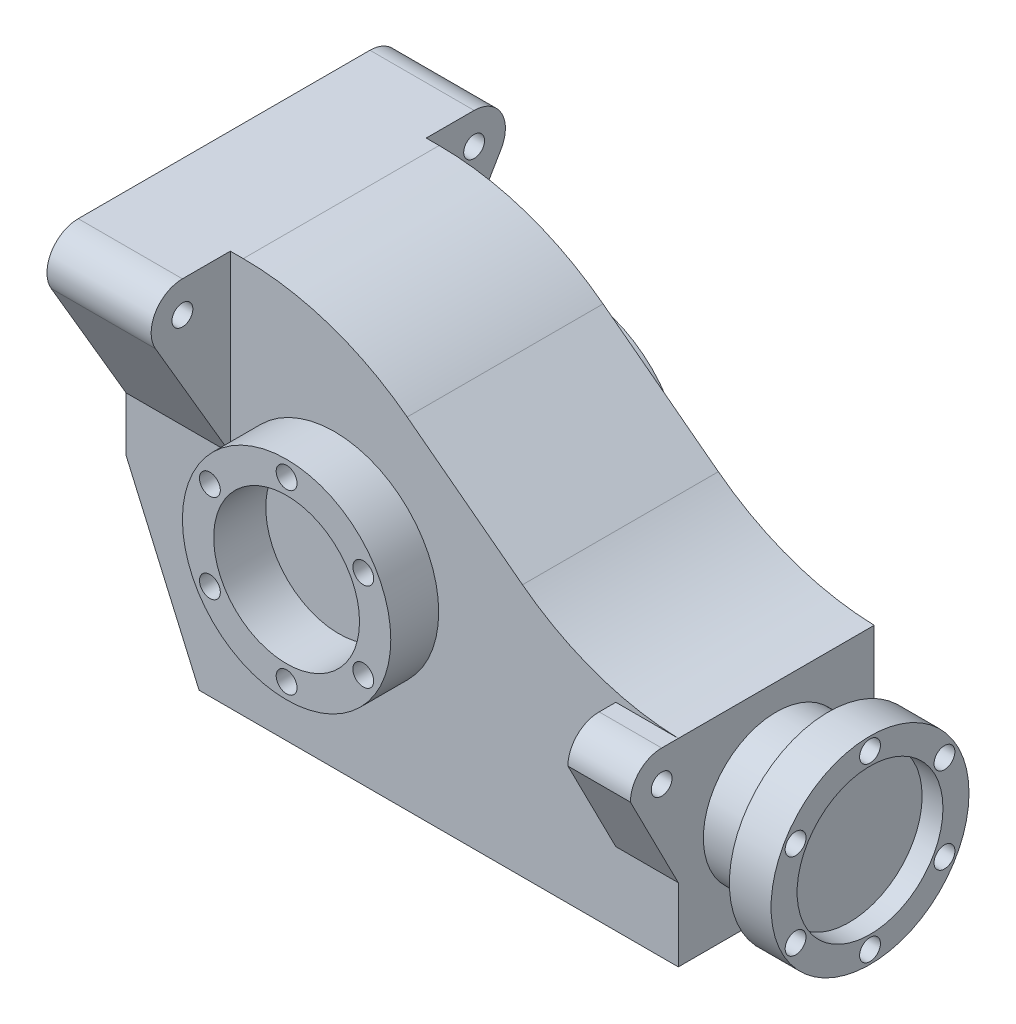
SolidWorks part; units mm, degrees
ref_plane "Płaszczyzna przednia" through (0, 0, 0) normal (0, 0, 1) x (1, 0, 0)
ref_plane "Płaszczyzna górna" through (0, 0, 0) normal (0, 1, 0) x (1, 0, 0)
ref_plane "Płaszczyzna prawa" through (0, 0, 0) normal (1, 0, 0) x (0, 0, -1)
sketch "Szkic1" plane through (0, 0, 0) normal (0, 0, 1) x (1, 0, 0)
  line L0 (-35, 190) -> (65, 190)
  line L1 (65, 190) -> (190, 95)
  line L2 (190, 95) -> (230, 95)
  line L3 (230, 95) -> (230, 0)
  line L4 (230, 0) -> (0, 0)
  line L7 (-35, 190) -> (-35, 80)
  line L8 (-35, 80) -> (0, 0)
  dimension "D1" = 265
  dimension "D2" = 190
  dimension "D3" = 95
  dimension "D4" = 80
  dimension "D5" = 230
  dimension "D6" = 100
  dimension "D7" = 40
extrude "Dodanie-wyciągnięcie1" add sketch "Szkic1" along normal mid plane 94 contours L1 L2 L3 L4 L8 L7 L0
sketch "Szkic2" plane through (230, 0, 0) normal (1, 0, 0) x (0, 0, -1)
  line L0 (-47, 95) -> (47, 0) construction
  line L1 (47, 95) -> (-47, 0) construction
  line L2 (-47, 0) -> (47, 0) construction
  circle A0 centre (0, 47.5) radius 35
  point P13 (0, 47.5)
  dimension "D1" = 70
extrude "Dodanie-wyciągnięcie2" add sketch "Szkic2" along normal blind 25 separate body
sketch "Szkic3" plane through (255, 0, 0) normal (1, 0, 0) x (0, 0, -1)
  circle A0 centre (0, 47.5) radius 47.5
  circle A1 centre (0, 47.5) radius 35 construction
  dimension "D1" = 95
extrude "Dodanie-wyciągnięcie3" add sketch "Szkic3" along normal blind 20
sketch "Szkic4" plane through (275, 0, 0) normal (1, 0, 0) x (0, 0, -1)
  circle A0 centre (0, 47.5) radius 35
  circle A1 centre (0, 47.5) radius 47.5 construction
  dimension "D1" = 70
sketch "Szkic7" plane through (0, 0, 47) normal (0, 0, 1) x (1, 0, 0)
  line L0 (-35, 190) -> (-35, 80) construction
  line L1 (-35, 190) -> (65, 190) construction
  circle A0 centre (65, 90) radius 50
  dimension "D1" = 100
  dimension "D2" = 100
  dimension "D3" = 100
extrude "Dodanie-wyciągnięcie5" add sketch "Szkic7" along normal blind 23
sketch "Szkic8" plane through (0, 0, 70) normal (0, 0, 1) x (1, 0, 0)
  circle A0 centre (65, 90) radius 35
  dimension "D1" = 70
extrude "Wytnij-wyciągnięcie1" cut sketch "Szkic8" against normal blind 25
sketch "Szkic9" plane through (0, 0, 70) normal (0, 0, 1) x (1, 0, 0)
  line L0 (65, 90) -> (65, 132.5) construction
  circle A0 centre (65, 132.5) radius 5
  circle A1 centre (101.8061, 111.25) radius 5
  circle A2 centre (65, 90) radius 35 construction
  circle A3 centre (65, 90) radius 35
  circle A4 centre (101.8061, 68.75) radius 5
  circle A5 centre (65, 47.5) radius 5
  circle A6 centre (28.1939, 68.75) radius 5
  circle A7 centre (28.1939, 111.25) radius 5
  dimension "D1" = 10
  dimension "D2" = 42.5
  dimension "D3" = 6
  dimension "D4" = 42.5
extrude "Wytnij-wyciągnięcie2" cut sketch "Szkic9" against normal blind 15 contours A0 | A1 | A4 | A5 | A6 | A7
sketch "Szkic12" plane through (-35, 0, 0) normal (-1, 0, 0) x (0, 0, 1)
  line L0 (-70, 190) -> (70, 190)
  line L1 (47, 190) -> (-47, 190) construction
  line L2 (-82.9419, 167.4166) -> (-20, 60)
  line L4 (47, 0) -> (-47, 0) construction
  line L5 (-20, 60) -> (20, 60)
  line L6 (0, 190) -> (0, 60) construction
  line L7 (82.9419, 167.4166) -> (20, 60)
  circle A0 centre (-70, 175) radius 5
  arc A1 (-70, 190) -> (-82.9419, 167.4166) centre (-70, 175) ccw
  arc A2 (70, 190) -> (82.9419, 167.4166) centre (70, 175) cw
  circle A3 centre (70, 175) radius 5
  line M4 (-47, 190) -> (-47, 80)
  line M5 (-47, 80) -> (47, 80)
  line M6 (47, 80) -> (47, 190)
  line M7 (47, 190) -> (-47, 190)
  dimension "D1" = 10
  dimension "D2" = 30
  dimension "D4" = 20
  dimension "D5" = 70
  dimension "D3" = 60
extrude "Dodanie-wyciągnięcie6" add sketch "Szkic12" against normal blind 50 contours L0 A1 L2 A0 M4 | L6 L0 L2 M4 M5 | L6 L7 M7 M5 M6 | A2 L0 L7 A3 M6 | L6 L5 L7 M5 | L6 L2 L5 M5 region at (-35, 159.5519, -61.1328) region at (-35, 136.8562, -22.7622) region at (-35, 136.8562, 22.7622) region at (-35, 159.5519, 61.1328) region at (-35, 70.7553, 13.1511) region at (-35, 70.7553, -13.1511)
mirror "Lustro1" about plane through (0, 0, 0) normal (0, 0, 1) of "Wytnij-wyciągnięcie2", "Wytnij-wyciągnięcie1", "Dodanie-wyciągnięcie5"
fillet "Zaokrąglenie2" radius 130 1 edges at (65, 190, 0)
fillet "Zaokrąglenie3" radius 130 1 edges at (190, 95, 0)
extrude "Wytnij-wyciągnięcie3" cut sketch "Szkic4" against normal blind 10
sketch "Szkic13" plane through (0, 0, 47) normal (0, 0, 1) x (1, 0, 0)
  line L0 (230, 95) -> (230, 0) construction
  line L1 (230, 95) -> (200, 95)
  line L2 (230, 95) -> (230, 35)
  line L3 (230, 35) -> (200, 35)
  line L4 (200, 95) -> (200, 35)
  dimension "D1" = 60
  dimension "D2" = 30
sketch "Szkic14" plane through (0, 0, 70) normal (0, 0, 1) x (1, 0, 0)
  line L1 (200, 95) -> (230, 95)
  line L2 (200, 95) -> (200, 60)
  line L3 (200, 60) -> (230, 60)
  line L4 (230, 95) -> (230, 60)
  line L5 (230, 95) -> (230, 35) construction
  dimension "D1" = 35
loft "Wyciągnięcie po profilach1" add profiles "Szkic13", "Szkic14"
sketch "Szkic15" plane through (230, 0, 0) normal (1, 0, 0) x (0, 0, -1)
  line L0 (-47, 95) -> (-70, 95) construction
  line L1 (-70, 60) -> (-70, 95) construction
  line L5 (-70, 80) -> (-70, 95)
  line L6 (-70, 95) -> (-55, 95)
  arc A0 (-55, 95) -> (-70, 80) centre (-55, 80) ccw
  dimension "D1" = 30
extrude "Wytnij-wyciągnięcie4" cut sketch "Szkic15" against normal up to next (30 mm away)
sketch "Szkic19" plane through (230, 0, 0) normal (1, 0, 0) x (0, 0, -1)
  line L0 (-70, 80) -> (-47, 35)
  line L1 (-47, 35) -> (-70, 60)
  line L2 (-70, 60) -> (-70, 80)
extrude "Wytnij-wyciągnięcie6" cut sketch "Szkic19" against normal up to next (30 mm away) contours L0 L1 L2
sketch "Szkic20" plane through (230, 0, 0) normal (1, 0, 0) x (0, 0, -1)
  circle A0 centre (-55, 80) radius 5
  arc A1 (-55, 95) -> (-70, 80) centre (-55, 80) ccw construction
  dimension "D1" = 10
extrude "Wytnij-wyciągnięcie7" cut sketch "Szkic20" against normal up to next (30 mm away)
sketch "Szkic21" plane through (275, 0, 0) normal (1, 0, 0) x (0, 0, -1)
  circle A0 centre (0, 88.75) radius 5
  circle A3 centre (0, 47.5) radius 35 construction
  dimension "D1" = 10
  dimension "D2" = 41.25
extrude "Wytnij-wyciągnięcie8" cut sketch "Szkic21" against normal blind 10
pattern_circular "Szyk kołowy1" count 6 over 360 about axis through (265, 47.5, 0) along (1, 0, 0) of "Wytnij-wyciągnięcie8"
